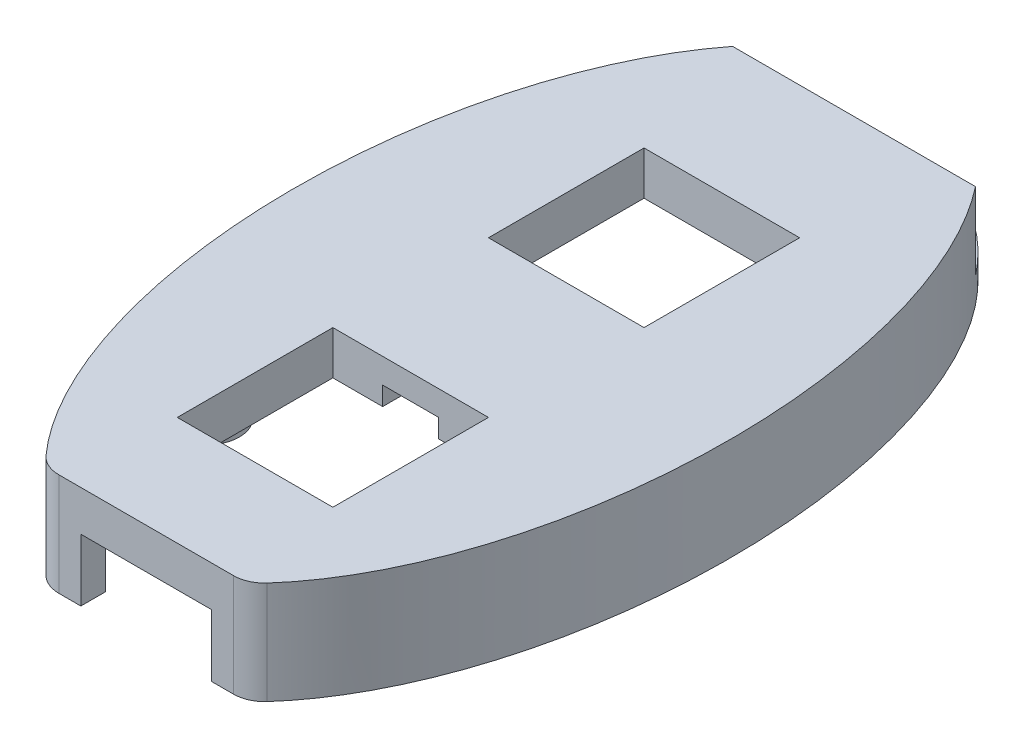
SolidWorks part; units mm, degrees
ref_plane "Front Plane" through (0, 0, 0) normal (0, 0, 1) x (1, 0, 0)
ref_plane "Top Plane" through (0, 0, 0) normal (0, 1, 0) x (1, 0, 0)
ref_plane "Right Plane" through (0, 0, 0) normal (1, 0, 0) x (0, 0, -1)
sketch "Sketch1" plane through (0, 0, 0) normal (0, 1, 0) x (1, 0, 0)
  line L0 (-8.2173, -29.845) -> (8.2173, -29.845)
  ellipse E0 centre (0, 0) end of major axis (0, -33.655) minor radius 17.78 (8.2173, -29.845) -> (-8.2173, -29.845) ccw
  dimension "D1" = 67.31
  dimension "D2" = 35.56
  dimension "D3" = 63.5
extrude "Boss-Extrude1" add sketch "Sketch1" against normal blind 2.032
sketch "Sketch17" plane through (0, 0, 0) normal (0, 1, 0) x (1, 0, 0)
  line L0 (0, 0) -> (0, 50.5429) construction
  line L1 (-6.35, 17.145) -> (6.35, 17.145)
  line L2 (-6.35, 17.145) -> (-6.35, 4.445)
  line L3 (-6.35, 4.445) -> (6.35, 4.445)
  line L4 (6.35, 17.145) -> (6.35, 4.445)
  line L5 (-6.35, 17.145) -> (6.35, 4.445) construction
  line L6 (-6.35, 4.445) -> (6.35, 17.145) construction
  line L7 (-6.35, -8.255) -> (6.35, -8.255)
  line L8 (-6.35, -8.255) -> (-6.35, -20.955)
  line L9 (-6.35, -20.955) -> (6.35, -20.955)
  line L10 (6.35, -8.255) -> (6.35, -20.955)
  line L11 (-6.35, -8.255) -> (6.35, -20.955) construction
  line L12 (-6.35, -20.955) -> (6.35, -8.255) construction
  line L13 (-8.2173, -29.845) -> (8.2173, -29.845) construction
  point P0 (0, 10.795)
  point P5 (0, -14.605)
  dimension "D1" = 12.7
  dimension "D2" = 15.24
  dimension "D3" = 40.64
extrude "Cut-Extrude13" cut sketch "Sketch17" against normal through all
sketch "Sketch18" plane through (0, -2.032, 0) normal (0, 1, 0) x (1, 0, 0)
  line L105 (-8.382, 19.177) -> (-8.382, 2.413)
  line L106 (-8.382, 2.413) -> (8.382, 2.413)
  line L107 (8.382, 2.413) -> (8.382, 19.177)
  line L108 (8.382, 19.177) -> (-8.382, 19.177)
  line L109 (-8.382, 19.177) -> (-8.382, 2.413)
  line L110 (-8.382, 2.413) -> (-2.286, 2.413)
  line L111 (8.382, 2.413) -> (8.382, 19.177)
  line L112 (8.382, 19.177) -> (-8.382, 19.177)
  line L113 (-6.35, 17.145) -> (-6.35, 4.445) construction
  line L114 (6.35, 17.145) -> (-6.35, 17.145) construction
  line L115 (-6.35, 4.445) -> (6.35, 4.445) construction
  line L116 (6.35, 4.445) -> (6.35, 17.145) construction
  line L117 (8.382, -22.987) -> (8.382, -6.223)
  line L118 (8.382, -6.223) -> (-8.382, -6.223)
  line L119 (-8.382, -6.223) -> (-8.382, -22.987)
  line L120 (-8.382, -22.987) -> (8.382, -22.987)
  line L121 (8.382, -22.987) -> (8.382, -6.223)
  line L122 (8.382, -6.223) -> (2.286, -6.223)
  line L123 (-8.382, -6.223) -> (-8.382, -22.987)
  line L124 (-8.382, -22.987) -> (8.382, -22.987)
  line L125 (-6.35, 17.145) -> (-6.35, 4.445)
  line L126 (6.35, 17.145) -> (-6.35, 17.145)
  line L127 (-6.35, 4.445) -> (-2.286, 4.445)
  line L128 (6.35, 4.445) -> (6.35, 17.145)
  line L129 (6.35, -8.255) -> (-6.35, -8.255) construction
  line L130 (6.35, -20.955) -> (6.35, -8.255) construction
  line L131 (-6.35, -20.955) -> (6.35, -20.955) construction
  line L132 (-6.35, -8.255) -> (-6.35, -20.955) construction
  line L133 (6.35, -8.255) -> (2.286, -8.255)
  line L134 (6.35, -20.955) -> (6.35, -8.255)
  line L135 (-6.35, -20.955) -> (6.35, -20.955)
  line L136 (-6.35, -8.255) -> (-6.35, -20.955)
  line L137 (-2.286, -8.255) -> (-2.286, -6.223)
  line L139 (2.286, 4.445) -> (2.286, 2.413)
  line L141 (0, 0) -> (0, 31.2149) construction
  line L142 (2.286, 2.413) -> (8.382, 2.413)
  line L143 (2.286, 4.445) -> (6.35, 4.445)
  line L144 (-2.286, -6.223) -> (-8.382, -6.223)
  line L145 (-2.286, -8.255) -> (-6.35, -8.255)
  line L146 (-2.286, 2.413) -> (-2.286, 4.445)
  line L147 (2.286, -6.223) -> (2.286, -8.255)
  dimension "D3" = 4.572
  dimension "D1" = 2.032
  dimension "D2" = 2.032
extrude "LightBox" add sketch "Sketch18" against normal blind 1.524
sketch "Sketch19" plane through (0, -2.032, 0) normal (0, -1, 0) x (1, 0, 0)
  line L0 (0, 0) -> (0, 18.966) construction
  circle A0 centre (-13.462, 11.43) radius 1.1303
  circle A1 centre (13.462, 11.43) radius 1.1303
  circle A2 centre (13.462, 11.43) radius 2.6543
  circle A3 centre (-13.462, 11.43) radius 2.6543
  dimension "D3" = 2.2606
  dimension "D1" = 11.43
  dimension "D2" = 26.924
  dimension "D4" = 1.524
extrude "Boss-Screws" add sketch "Sketch19" along normal blind 6.35
sketch "Sketch20" plane through (0, -2.032, 0) normal (0, -1, 0) x (1, 0, 0)
  line L0 (-8.2173, 29.845) -> (8.2173, 29.845) construction
  line L1 (-8.2173, 29.845) -> (8.2173, 29.845)
  line L2 (-7.3554, 27.813) -> (7.3554, 27.813)
  ellipse E0 centre (0, 0) end of major axis (0, 33.655) minor radius 17.78 (-8.2173, 29.845) -> (8.2173, 29.845) ccw construction
  ellipse E1 centre (0, 0) end of major axis (0, 33.655) minor radius 17.78 (-8.2173, 29.845) -> (8.2173, 29.845) ccw
  spline S0 degree 1 poles (-7.3554, 27.813) (7.3554, 27.813) knots 0 0 1 1 construction
  spline S1 degree 3 poles (-7.3554, 27.813) (-7.747, 27.3876) (-8.4711, 26.523) (-9.5515, 24.9917) (-10.5644, 23.2899) (-11.8281, 20.7908) (-13.2119, 17.2782) (-14.4988, 12.5627) (-15.3664, 7.4855) (-15.9268, 0.4294) (-15.4665, -8.5478) (-13.1226, -18.3463) (-9.3021, -26.0406) (-5.4001, -29.9288) (-2.2834, -31.3895) (0, -31.7398) (2.2834, -31.3895) (5.4001, -29.9288) (9.3021, -26.0406) (13.1226, -18.3463) (15.4665, -8.5478) (15.9268, 0.4294) (15.3664, 7.4855) (14.4988, 12.5627) (13.2119, 17.2782) (11.8281, 20.7908) (10.5644, 23.2899) (9.5515, 24.9917) (8.4711, 26.523) (7.747, 27.3876) (7.3554, 27.813) knots 0.521032 0.521032 0.521032 0.521032 0.602925 0.684817 0.76671 0.848602 1.012387 1.176172 1.339957 1.503742 1.831312 2.158882 2.486453 2.814023 2.977808 3.141593 3.305378 3.469163 3.796733 4.124303 4.451873 4.779443 4.943228 5.107013 5.270798 5.434583 5.516476 5.598368 5.680261 5.762153 5.762153 5.762153 5.762153
  dimension "D1" = 2.032
extrude "FlangeOuter" add sketch "Sketch20" along normal blind 6.35
sketch "Sketch21" plane through (0, 0, 29.845) normal (0, 0, 1) x (1, 0, 0)
  line L0 (8.2173, -8.382) -> (-8.2173, -8.382) construction
  line L1 (-5.334, -8.382) -> (5.334, -8.382)
  line L2 (-5.334, -8.382) -> (-5.334, -3.302)
  line L3 (-5.334, -3.302) -> (5.334, -3.302)
  line L4 (5.334, -8.382) -> (5.334, -3.302)
  line L5 (0, 0) -> (0, -14.4473) construction
  line L6 (-8.2173, 0) -> (8.2173, 0) construction
  dimension "D1" = 5.08
  dimension "D2" = 10.668
extrude "Cut-Extrude14" cut sketch "Sketch21" against normal up to next
sketch "Sketch22" plane through (0, 0, 0) normal (0, 1, 0) x (1, 0, 0)
  line L0 (0, 0) -> (0, 47.2593) construction
  line L1 (-25.4, 53.34) -> (25.4, 53.34)
  line L2 (-25.4, 53.34) -> (-25.4, 27.94)
  line L3 (-25.4, 27.94) -> (25.4, 27.94)
  line L4 (25.4, 53.34) -> (25.4, 27.94)
  dimension "D1" = 27.94
  dimension "D2" = 25.4
  dimension "D3" = 50.8
extrude "Cut-Extrude15" cut sketch "Sketch22" against normal offset from surface (6.35 mm away) 2.032 up to face at (-0.693, -8.382, 17.6865)
sketch "Sketch25" plane through (0, -6.35, 0) normal (0, 1, 0) x (1, 0, 0)
  line L0 (-9.2845, 28.702) -> (9.2845, 28.702)
  line L1 (-9.912, 27.94) -> (9.912, 27.94) construction
  ellipse E0 centre (0, 0) end of major axis (0, -33.655) minor radius 17.78 (9.912, 27.94) -> (-9.912, 27.94) ccw construction
  ellipse E1 centre (0, 0) end of major axis (0, -33.655) minor radius 17.78 (9.2845, 28.702) -> (-9.2845, 28.702) ccw
  dimension "D1" = 0.762
extrude "Boss-Extrude8" add sketch "Sketch25" against normal through all
fillet "Fillet1" radius 2.54 2 edges at (8.2173, -4.191, 29.845) (-8.2173, -4.191, 29.845)
